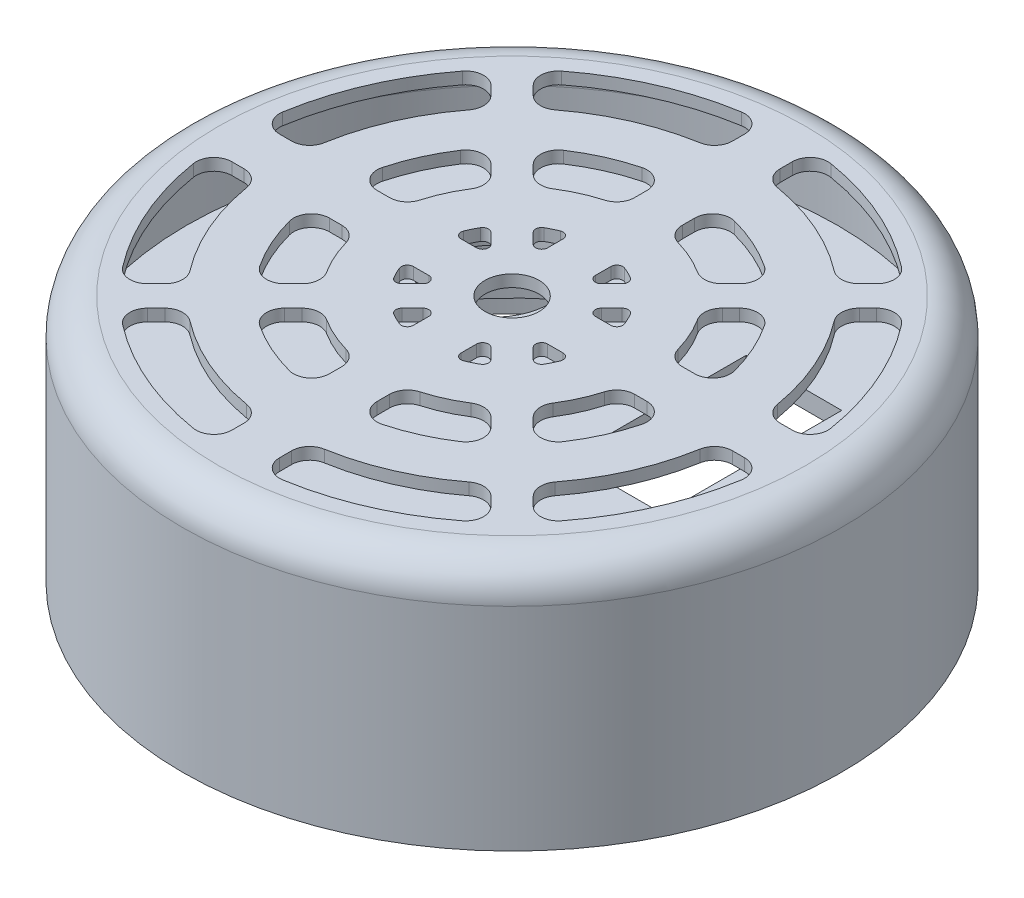
SolidWorks part; units mm, degrees
ref_plane "Front Plane" through (0, 0, 0) normal (0, 0, 1) x (1, 0, 0)
ref_plane "Top Plane" through (0, 0, 0) normal (0, 1, 0) x (1, 0, 0)
ref_plane "Right Plane" through (0, 0, 0) normal (1, 0, 0) x (0, 0, -1)
sketch "Sketch1" plane through (0, 0, 0) normal (0, 1, 0) x (1, 0, 0)
  circle A1 centre (0, 0) radius 55.2
  dimension "D2" = 110.4
extrude "Boss-Extrude1" add sketch "Sketch1" along normal blind 3
sketch "Sketch2" plane through (0, 3, 0) normal (0, 1, 0) x (1, 0, 0)
  circle A0 centre (0, 0) radius 55
  dimension "D1" = 110
extrude "Cut-Extrude1" cut sketch "Sketch2" against normal through all
sketch "Sketch4" plane through (0, 3, 0) normal (0, 1, 0) x (1, 0, 0)
  line L0 (0, 0) -> (8.2385, 0) construction
  line L1 (8.2385, 0) -> (0, 0) construction
  line L2 (0, 0) -> (0, 11.6273) construction
  line L3 (-45.2, -5) -> (-45.2, 5)
  line L4 (-45.2, -5) -> (-53.768, -5)
  line L5 (-45.2, 5) -> (-53.768, 5)
  circle A1 centre (0, 0) radius 55.2
  circle A2 centre (0, 0) radius 55.2
  arc A3 (-53.768, -5) -> (-53.768, 5) centre (0, 0) ccw
  point P12 (-45.2, 0)
  dimension "D2" = 110.4
  dimension "D3" = 108
  dimension "D4" = 10
  dimension "D5" = 10
  dimension "D1" = 0
extrude "Boss-Extrude2" add sketch "Sketch4" along normal blind 18.5
sketch "Sketch8" plane through (0, 3, 0) normal (0, -1, 0) x (1, 0, 0)
  line L2 (-53.768, -5) -> (-45.2, -5) construction
  line L3 (-45.2, 5) -> (-54.7723, 5)
  line L4 (-45.2, 5) -> (-45.2, -5)
  line L5 (-45.2, -5) -> (-54.7723, -5)
  circle A2 centre (0, 0) radius 55 construction
  arc A3 (-54.7723, 5) -> (-54.7723, -5) centre (0, 0) ccw
extrude "Boss-Extrude4" add sketch "Sketch8" along normal blind 3
sketch "Sketch6" plane through (0, 21.5, 0) normal (0, 1, 0) x (1, 0, 0)
  line L1 (11.2131, 28) -> (27.2131, 28)
  line L2 (11.2131, 28) -> (11.2131, -2)
  line L3 (11.2131, -2) -> (27.2131, -2)
  line L4 (27.2131, 28) -> (27.2131, -2)
  line L5 (11.2131, 28) -> (27.2131, -2) construction
  line L6 (11.2131, -2) -> (27.2131, 28) construction
  line L7 (12.1174, 28) -> (26.3174, 28) construction
  circle A0 centre (0, 0) radius 55.2
  circle A1 centre (-22.2011, 19.0599) radius 9.5
  point P5 (19.2131, 13)
  dimension "D1" = 19
  dimension "D2" = 30
  dimension "D3" = 16
  dimension "D6" = 110.4
  dimension "D4" = 19.2131
  dimension "D5" = 13
  dimension "D7" = 19.0599
  dimension "D8" = 22.2011
extrude "Boss-Extrude3" add sketch "Sketch6" along normal blind 3
sketch "Sketch9" plane through (0, 24.5, 0) normal (0, 1, 0) x (1, 0, 0)
  circle A0 centre (0, 0) radius 55.2
  circle A1 centre (0, 0) radius 54.5
  dimension "D1" = 110.4
  dimension "D2" = 109
extrude "Boss-Extrude5" add sketch "Sketch9" along normal blind 15
sketch "Sketch10" plane through (0, 39.5, 0) normal (0, 1, 0) x (1, 0, 0)
  line L0 (0, 0) -> (18.0348, 0) construction
  line L2 (0, 0) -> (0, 14.913) construction
  line L5 (0, 0) -> (-39.0323, 39.0323) construction
  line L10 (-4, 40.9054) -> (-4, 42.9331)
  line L11 (-4, 24.5204) -> (-4, 26.5942)
  line L12 (-4, 9.9497) -> (-4, 12.5399)
  line L14 (-12.5399, 4) -> (-9.9497, 4)
  line L15 (-26.5942, 4) -> (-24.5204, 4)
  line L16 (-42.9331, 4) -> (-40.9054, 4)
  line L21 (-27.3183, 30.8538) -> (-28.7445, 32.2801)
  line L22 (-30.8538, 27.3183) -> (-32.2801, 28.7445)
  line L23 (-15.839, 19.3746) -> (-17.2848, 20.8203)
  line L24 (-19.3746, 15.839) -> (-20.8203, 17.2848)
  line L25 (-5.7071, 9.2426) -> (-7.4518, 10.9873)
  line L26 (-9.2426, 5.7071) -> (-10.9873, 7.4518)
  line L51 (9.2426, 5.7071) -> (10.9873, 7.4518)
  line L52 (12.5399, 4) -> (9.9497, 4)
  line L53 (5.7071, 9.2426) -> (7.4518, 10.9873)
  line L54 (4, 9.9497) -> (4, 12.5399)
  line L55 (4, 24.5204) -> (4, 26.5942)
  line L56 (15.839, 19.3746) -> (17.2848, 20.8203)
  line L57 (19.3746, 15.839) -> (20.8203, 17.2848)
  line L58 (26.5942, 4) -> (24.5204, 4)
  line L59 (42.9331, 4) -> (40.9054, 4)
  line L60 (30.8538, 27.3183) -> (32.2801, 28.7445)
  line L61 (4, 40.9054) -> (4, 42.9331)
  line L62 (27.3183, 30.8538) -> (28.7445, 32.2801)
  line L63 (30.8538, -27.3183) -> (32.2801, -28.7445)
  line L64 (42.9331, -4) -> (40.9054, -4)
  line L65 (26.5942, -4) -> (24.5204, -4)
  line L66 (19.3746, -15.839) -> (20.8203, -17.2848)
  line L67 (9.2426, -5.7071) -> (10.9873, -7.4518)
  line L68 (12.5399, -4) -> (9.9497, -4)
  line L69 (-9.2426, -5.7071) -> (-10.9873, -7.4518)
  line L70 (-12.5399, -4) -> (-9.9497, -4)
  line L71 (-5.7071, -9.2426) -> (-7.4518, -10.9873)
  line L72 (-4, -9.9497) -> (-4, -12.5399)
  line L73 (4, -9.9497) -> (4, -12.5399)
  line L74 (5.7071, -9.2426) -> (7.4518, -10.9873)
  line L75 (4, -24.5204) -> (4, -26.5942)
  line L76 (15.839, -19.3746) -> (17.2848, -20.8203)
  line L77 (4, -40.9054) -> (4, -42.9331)
  line L78 (27.3183, -30.8538) -> (28.7445, -32.2801)
  line L79 (-4, -24.5204) -> (-4, -26.5942)
  line L80 (-15.839, -19.3746) -> (-17.2848, -20.8203)
  line L81 (-19.3746, -15.839) -> (-20.8203, -17.2848)
  line L82 (-26.5942, -4) -> (-24.5204, -4)
  line L83 (-42.9331, -4) -> (-40.9054, -4)
  line L84 (-30.8538, -27.3183) -> (-32.2801, -28.7445)
  line L85 (-4, -40.9054) -> (-4, -42.9331)
  line L86 (-27.3183, -30.8538) -> (-28.7445, -32.2801)
  circle A0 centre (0, 0) radius 55.2
  arc A1 (-36.7739, 28.4593) -> (-45.894, 7.4828) centre (0, 0) ccw
  circle A2 centre (0, 0) radius 54.5 construction
  arc A3 (-30.5914, 23.3755) -> (-37.9484, 6.494) centre (0, 0) ccw
  circle A7 centre (0, 0) radius 4.5314
  arc A10 (-25.4444, 16.8177) -> (-29.4954, 7.7636) centre (0, 0) ccw
  arc A11 (-18.967, 12.1039) -> (-21.6356, 6.1765) centre (0, 0) ccw
  arc A12 (-7.4828, 45.894) -> (-28.4593, 36.7739) centre (0, 0) ccw
  arc A13 (-6.494, 37.9484) -> (-23.3755, 30.5914) centre (0, 0) ccw
  arc A14 (-7.7636, 29.4954) -> (-16.8177, 25.4444) centre (0, 0) ccw
  arc A15 (-6.1765, 21.6356) -> (-12.1039, 18.967) centre (0, 0) ccw
  arc A16 (-5.3704, 13.4688) -> (-7.2443, 12.5607) centre (0, 0) ccw
  arc A17 (-12.5607, 7.2443) -> (-13.4688, 5.3704) centre (0, 0) ccw
  arc A46 (-4, 24.5204) -> (-6.1765, 21.6356) centre (-7, 24.5204) cw
  arc A47 (-15.839, 19.3746) -> (-12.1039, 18.967) centre (-13.7177, 21.4959) ccw
  arc A48 (-16.8177, 25.4444) -> (-17.2848, 20.8203) centre (-15.1635, 22.9416) ccw
  arc A49 (-7.7636, 29.4954) -> (-4, 26.5942) centre (-7, 26.5942) cw
  arc A50 (-4, 40.9054) -> (-6.494, 37.9484) centre (-7, 40.9054) cw
  arc A51 (-7.4828, 45.894) -> (-4, 42.9331) centre (-7, 42.9331) cw
  arc A52 (-28.4593, 36.7739) -> (-28.7445, 32.2801) centre (-26.6232, 34.4014) ccw
  arc A53 (-27.3183, 30.8538) -> (-23.3755, 30.5914) centre (-25.197, 32.9752) ccw
  arc A54 (-25.4444, 16.8177) -> (-20.8203, 17.2848) centre (-22.9416, 15.1635) cw
  arc A55 (-19.3746, 15.839) -> (-18.967, 12.1039) centre (-21.4959, 13.7177) cw
  arc A56 (-21.6356, 6.1765) -> (-24.5204, 4) centre (-24.5204, 7) cw
  arc A57 (-26.5942, 4) -> (-29.4954, 7.7636) centre (-26.5942, 7) cw
  arc A58 (-37.9484, 6.494) -> (-40.9054, 4) centre (-40.9054, 7) cw
  arc A59 (-30.8538, 27.3183) -> (-30.5914, 23.3755) centre (-32.9752, 25.197) cw
  arc A60 (-42.9331, 4) -> (-45.894, 7.4828) centre (-42.9331, 7) cw
  arc A61 (-36.7739, 28.4593) -> (-32.2801, 28.7445) centre (-34.4014, 26.6232) cw
  arc A62 (-5.7071, 9.2426) -> (-4, 9.9497) centre (-5, 9.9497) ccw
  arc A63 (-9.2426, 5.7071) -> (-9.9497, 4) centre (-9.9497, 5) cw
  arc A64 (-12.5607, 7.2443) -> (-10.9873, 7.4518) centre (-11.6944, 6.7447) cw
  arc A65 (-12.5399, 4) -> (-13.4688, 5.3704) centre (-12.5399, 5) cw
  arc A66 (-7.2443, 12.5607) -> (-7.4518, 10.9873) centre (-6.7447, 11.6944) ccw
  arc A67 (-5.3704, 13.4688) -> (-4, 12.5399) centre (-5, 12.5399) cw
  arc A68 (12.5607, 7.2443) -> (13.4688, 5.3704) centre (0, 0) cw
  arc A69 (12.5607, 7.2443) -> (10.9873, 7.4518) centre (11.6944, 6.7447) ccw
  arc A70 (9.2426, 5.7071) -> (9.9497, 4) centre (9.9497, 5) ccw
  arc A71 (12.5399, 4) -> (13.4688, 5.3704) centre (12.5399, 5) ccw
  arc A72 (7.2443, 12.5607) -> (7.4518, 10.9873) centre (6.7447, 11.6944) cw
  arc A73 (5.3704, 13.4688) -> (7.2443, 12.5607) centre (0, 0) cw
  arc A74 (5.7071, 9.2426) -> (4, 9.9497) centre (5, 9.9497) cw
  arc A75 (5.3704, 13.4688) -> (4, 12.5399) centre (5, 12.5399) ccw
  arc A76 (6.1765, 21.6356) -> (12.1039, 18.967) centre (0, 0) cw
  arc A77 (4, 24.5204) -> (6.1765, 21.6356) centre (7, 24.5204) ccw
  arc A78 (7.7636, 29.4954) -> (4, 26.5942) centre (7, 26.5942) ccw
  arc A79 (7.7636, 29.4954) -> (16.8177, 25.4444) centre (0, 0) cw
  arc A80 (15.839, 19.3746) -> (12.1039, 18.967) centre (13.7177, 21.4959) cw
  arc A81 (16.8177, 25.4444) -> (17.2848, 20.8203) centre (15.1635, 22.9416) cw
  arc A82 (25.4444, 16.8177) -> (20.8203, 17.2848) centre (22.9416, 15.1635) ccw
  arc A83 (25.4444, 16.8177) -> (29.4954, 7.7636) centre (0, 0) cw
  arc A84 (26.5942, 4) -> (29.4954, 7.7636) centre (26.5942, 7) ccw
  arc A85 (19.3746, 15.839) -> (18.967, 12.1039) centre (21.4959, 13.7177) ccw
  arc A86 (21.6356, 6.1765) -> (24.5204, 4) centre (24.5204, 7) ccw
  arc A87 (18.967, 12.1039) -> (21.6356, 6.1765) centre (0, 0) cw
  arc A88 (30.5914, 23.3755) -> (37.9484, 6.494) centre (0, 0) cw
  arc A89 (37.9484, 6.494) -> (40.9054, 4) centre (40.9054, 7) ccw
  arc A90 (42.9331, 4) -> (45.894, 7.4828) centre (42.9331, 7) ccw
  arc A91 (36.7739, 28.4593) -> (45.894, 7.4828) centre (0, 0) cw
  arc A92 (30.8538, 27.3183) -> (30.5914, 23.3755) centre (32.9752, 25.197) ccw
  arc A93 (36.7739, 28.4593) -> (32.2801, 28.7445) centre (34.4014, 26.6232) ccw
  arc A94 (6.494, 37.9484) -> (23.3755, 30.5914) centre (0, 0) cw
  arc A95 (4, 40.9054) -> (6.494, 37.9484) centre (7, 40.9054) ccw
  arc A96 (7.4828, 45.894) -> (4, 42.9331) centre (7, 42.9331) ccw
  arc A97 (7.4828, 45.894) -> (28.4593, 36.7739) centre (0, 0) cw
  arc A98 (28.4593, 36.7739) -> (28.7445, 32.2801) centre (26.6232, 34.4014) cw
  arc A99 (27.3183, 30.8538) -> (23.3755, 30.5914) centre (25.197, 32.9752) cw
  arc A100 (30.8538, -27.3183) -> (30.5914, -23.3755) centre (32.9752, -25.197) cw
  arc A101 (36.7739, -28.4593) -> (32.2801, -28.7445) centre (34.4014, -26.6232) cw
  arc A102 (36.7739, -28.4593) -> (45.894, -7.4828) centre (0, 0) ccw
  arc A103 (42.9331, -4) -> (45.894, -7.4828) centre (42.9331, -7) cw
  arc A104 (37.9484, -6.494) -> (40.9054, -4) centre (40.9054, -7) cw
  arc A105 (30.5914, -23.3755) -> (37.9484, -6.494) centre (0, 0) ccw
  arc A106 (19.3746, -15.839) -> (18.967, -12.1039) centre (21.4959, -13.7177) cw
  arc A107 (18.967, -12.1039) -> (21.6356, -6.1765) centre (0, 0) ccw
  arc A108 (21.6356, -6.1765) -> (24.5204, -4) centre (24.5204, -7) cw
  arc A109 (26.5942, -4) -> (29.4954, -7.7636) centre (26.5942, -7) cw
  arc A110 (25.4444, -16.8177) -> (29.4954, -7.7636) centre (0, 0) ccw
  arc A111 (25.4444, -16.8177) -> (20.8203, -17.2848) centre (22.9416, -15.1635) cw
  arc A112 (12.5607, -7.2443) -> (10.9873, -7.4518) centre (11.6944, -6.7447) cw
  arc A113 (9.2426, -5.7071) -> (9.9497, -4) centre (9.9497, -5) cw
  arc A114 (12.5399, -4) -> (13.4688, -5.3704) centre (12.5399, -5) cw
  arc A115 (12.5607, -7.2443) -> (13.4688, -5.3704) centre (0, 0) ccw
  arc A116 (-12.5607, -7.2443) -> (-13.4688, -5.3704) centre (0, 0) cw
  arc A117 (-12.5607, -7.2443) -> (-10.9873, -7.4518) centre (-11.6944, -6.7447) ccw
  arc A118 (-9.2426, -5.7071) -> (-9.9497, -4) centre (-9.9497, -5) ccw
  arc A119 (-12.5399, -4) -> (-13.4688, -5.3704) centre (-12.5399, -5) ccw
  arc A120 (-7.2443, -12.5607) -> (-7.4518, -10.9873) centre (-6.7447, -11.6944) cw
  arc A121 (-5.3704, -13.4688) -> (-7.2443, -12.5607) centre (0, 0) cw
  arc A122 (-5.7071, -9.2426) -> (-4, -9.9497) centre (-5, -9.9497) cw
  arc A123 (-5.3704, -13.4688) -> (-4, -12.5399) centre (-5, -12.5399) ccw
  arc A124 (5.7071, -9.2426) -> (4, -9.9497) centre (5, -9.9497) ccw
  arc A125 (5.3704, -13.4688) -> (4, -12.5399) centre (5, -12.5399) cw
  arc A126 (5.3704, -13.4688) -> (7.2443, -12.5607) centre (0, 0) ccw
  arc A127 (7.2443, -12.5607) -> (7.4518, -10.9873) centre (6.7447, -11.6944) ccw
  arc A128 (4, -24.5204) -> (6.1765, -21.6356) centre (7, -24.5204) cw
  arc A129 (7.7636, -29.4954) -> (4, -26.5942) centre (7, -26.5942) cw
  arc A130 (7.7636, -29.4954) -> (16.8177, -25.4444) centre (0, 0) ccw
  arc A131 (16.8177, -25.4444) -> (17.2848, -20.8203) centre (15.1635, -22.9416) ccw
  arc A132 (15.839, -19.3746) -> (12.1039, -18.967) centre (13.7177, -21.4959) ccw
  arc A133 (6.1765, -21.6356) -> (12.1039, -18.967) centre (0, 0) ccw
  arc A134 (4, -40.9054) -> (6.494, -37.9484) centre (7, -40.9054) cw
  arc A135 (7.4828, -45.894) -> (4, -42.9331) centre (7, -42.9331) cw
  arc A136 (7.4828, -45.894) -> (28.4593, -36.7739) centre (0, 0) ccw
  arc A137 (28.4593, -36.7739) -> (28.7445, -32.2801) centre (26.6232, -34.4014) ccw
  arc A138 (27.3183, -30.8538) -> (23.3755, -30.5914) centre (25.197, -32.9752) ccw
  arc A139 (6.494, -37.9484) -> (23.3755, -30.5914) centre (0, 0) ccw
  arc A140 (-6.1765, -21.6356) -> (-12.1039, -18.967) centre (0, 0) cw
  arc A141 (-4, -24.5204) -> (-6.1765, -21.6356) centre (-7, -24.5204) ccw
  arc A142 (-7.7636, -29.4954) -> (-4, -26.5942) centre (-7, -26.5942) ccw
  arc A143 (-7.7636, -29.4954) -> (-16.8177, -25.4444) centre (0, 0) cw
  arc A144 (-15.839, -19.3746) -> (-12.1039, -18.967) centre (-13.7177, -21.4959) cw
  arc A145 (-16.8177, -25.4444) -> (-17.2848, -20.8203) centre (-15.1635, -22.9416) cw
  arc A146 (-25.4444, -16.8177) -> (-20.8203, -17.2848) centre (-22.9416, -15.1635) ccw
  arc A147 (-25.4444, -16.8177) -> (-29.4954, -7.7636) centre (0, 0) cw
  arc A148 (-26.5942, -4) -> (-29.4954, -7.7636) centre (-26.5942, -7) ccw
  arc A149 (-19.3746, -15.839) -> (-18.967, -12.1039) centre (-21.4959, -13.7177) ccw
  arc A150 (-21.6356, -6.1765) -> (-24.5204, -4) centre (-24.5204, -7) ccw
  arc A151 (-18.967, -12.1039) -> (-21.6356, -6.1765) centre (0, 0) cw
  arc A152 (-30.5914, -23.3755) -> (-37.9484, -6.494) centre (0, 0) cw
  arc A153 (-37.9484, -6.494) -> (-40.9054, -4) centre (-40.9054, -7) ccw
  arc A154 (-42.9331, -4) -> (-45.894, -7.4828) centre (-42.9331, -7) ccw
  arc A155 (-36.7739, -28.4593) -> (-45.894, -7.4828) centre (0, 0) cw
  arc A156 (-30.8538, -27.3183) -> (-30.5914, -23.3755) centre (-32.9752, -25.197) ccw
  arc A157 (-36.7739, -28.4593) -> (-32.2801, -28.7445) centre (-34.4014, -26.6232) ccw
  arc A158 (-6.494, -37.9484) -> (-23.3755, -30.5914) centre (0, 0) cw
  arc A159 (-4, -40.9054) -> (-6.494, -37.9484) centre (-7, -40.9054) ccw
  arc A160 (-7.4828, -45.894) -> (-4, -42.9331) centre (-7, -42.9331) ccw
  arc A161 (-7.4828, -45.894) -> (-28.4593, -36.7739) centre (0, 0) cw
  arc A162 (-28.4593, -36.7739) -> (-28.7445, -32.2801) centre (-26.6232, -34.4014) cw
  arc A163 (-27.3183, -30.8538) -> (-23.3755, -30.5914) centre (-25.197, -32.9752) cw
  point P18 (0, 0)
  point P24 (-4, 30.2366)
  point P29 (-4, 38.2916)
  point P34 (-4, 46.3276)
  point P73 (-4, 7.5355)
  dimension "D1" = 110.4
  dimension "D2" = 8
  dimension "D3" = 8
  dimension "D4" = 8.0551
  dimension "D5" = 8
  dimension "D6" = 4
  dimension "D7" = 8
  dimension "D9" = 8
  dimension "D11" = 2.5
  dimension "D14" = 4
  dimension "D12" = 5.9686
  dimension "D13" = 3
  dimension "D16" = 1
  dimension "D8" = 45
  dimension "D10" = 2.5
  dimension "D15" = 4
extrude "Boss-Extrude6" add sketch "Sketch10" along normal blind 2
sketch "Sketch15" plane through (0, 3, 0) normal (0, -1, 0) x (1, 0, 0)
  line L0 (0, 0) -> (0, 9.6411) construction
  line L1 (0, 0) -> (7.7973, 0) construction
  circle A1 centre (0, 42) radius 3
  circle A3 centre (0, -37) radius 3
  point P1 (0, 0)
  dimension "D2" = 37
  dimension "D4" = 6
  dimension "D1" = 6
  dimension "D3" = 42
extrude "Boss-Extrude9" add sketch "Sketch15" against normal up to next
hole_wizard "Ø3.0mm Dowel Hole2" positions "3DSketch4" profile "Sketch17" hole size "Ø3.0" standard "DIN"
sketch3d "3DSketch4"
  line L0 (0, 21.5, 42) -> (0, 3, 42) construction
  line L1 (0, 21.5, -37) -> (0, 3, -37) construction
  point P0 (0, 3, 42)
  point P4 (0, 3, -37)
sketch "Sketch17" plane through (0, 3, 42) normal (1, 0, 0) x (0, 0, -1)
  line L0 (0, 0) -> (0, 14.9013)
  line L1 (0, 14.9013) -> (1.5, 14)
  line L2 (1.5, 14) -> (1.5, 0)
  line L5 (1.5, 0) -> (0, 0)
  line L10 (0, 14.9013) -> (-1.5, 14) construction
  line L11 (0, -6.35) -> (0, 107.95) construction
  dimension "Hole Dia." = 3
  dimension "Hole Depth" = 14
  dimension "Drill Angle" = 118
fillet "Fillet3" radius 6 2 edges at (0, 39.5, 54.5) (0, 41.5, 55.2)
